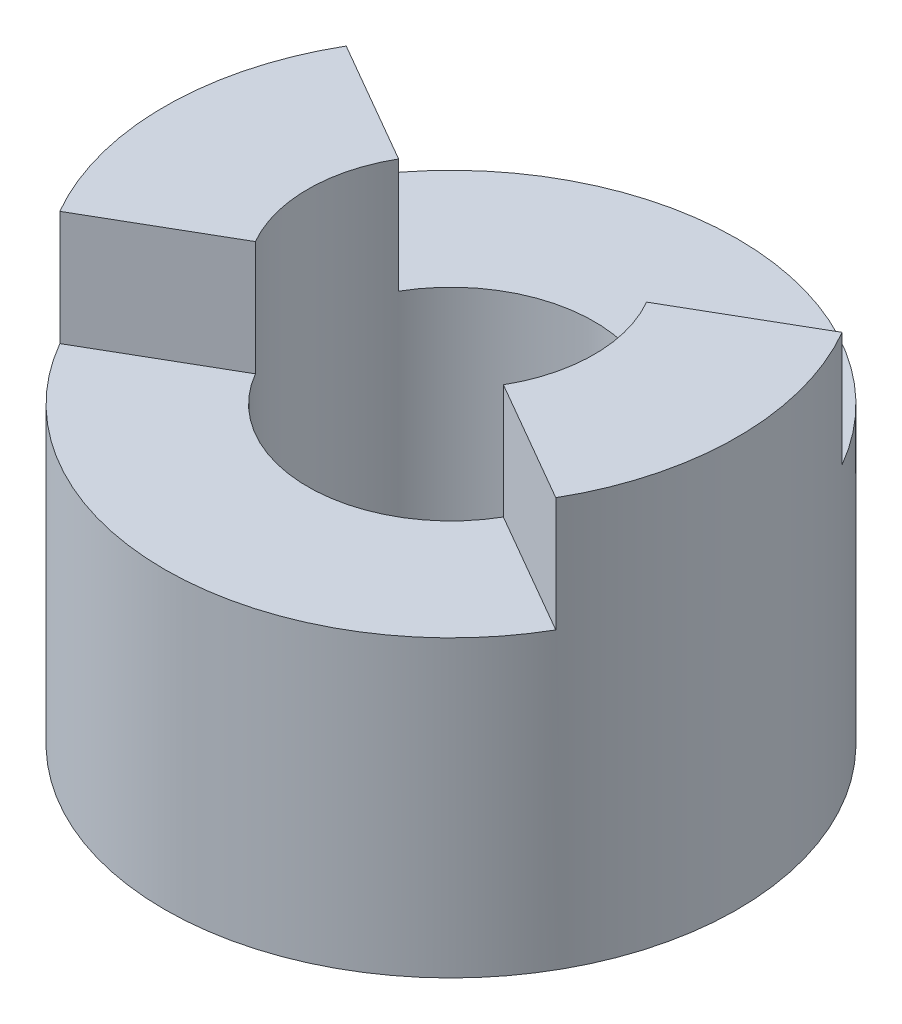
SolidWorks part; units mm, degrees
ref_plane "Front Plane" through (0, 0, 0) normal (0, 0, 1) x (1, 0, 0)
ref_plane "Top Plane" through (0, 0, 0) normal (0, 1, 0) x (1, 0, 0)
ref_plane "Right Plane" through (0, 0, 0) normal (1, 0, 0) x (0, 0, -1)
sketch "Sketch1" plane through (0, 0, 0) normal (0, 1, 0) x (1, 0, 0)
  circle A0 centre (0, 0) radius 35
  circle A1 centre (0, 0) radius 17.5
  dimension "D1" = 70
  dimension "D2" = 35
extrude "Boss-Extrude1" add sketch "Sketch1" along normal blind 50
sketch "Sketch2" plane through (0, 50, 0) normal (0, 1, 0) x (1, 0, 0)
  line L0 (0, 0) -> (45.0155, 0) construction
  line L1 (0, 0) -> (0, -60.2355) construction
  line L2 (15.1554, -8.75) -> (30.3109, -17.5)
  line L3 (-15.1554, -8.75) -> (-30.3109, -17.5)
  circle A0 centre (0, 0) radius 35 construction
  arc A1 (-30.3109, -17.5) -> (30.3109, -17.5) centre (0, 0) ccw
  circle A2 centre (0, 0) radius 17.5 construction
  arc A3 (-15.1554, -8.75) -> (15.1554, -8.75) centre (0, 0) ccw
  dimension "D1" = 120
extrude "Cut-Extrude1" cut sketch "Sketch2" against normal offset from surface (14 mm away) 36 up to face at (0, 0, 35)
ref_axis "Axis1" through (0, 50, 0) along (0, -1, 0)
mirror "Mirror1" about plane through (0, 0, 0) normal (0, 0, 1) of "Cut-Extrude1"
